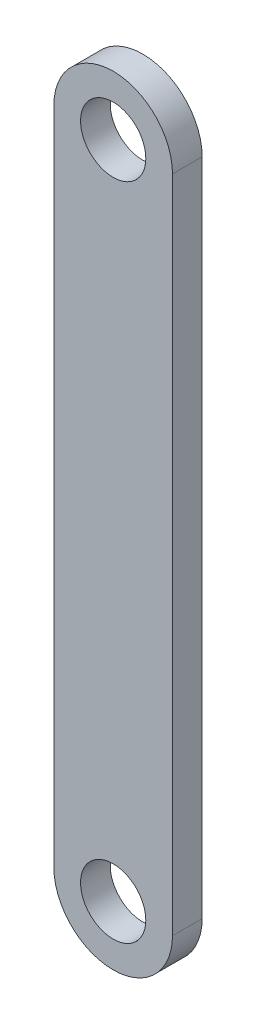
SolidWorks part; units mm, degrees
ref_plane "Спереди" through (0, 0, 0) normal (0, 0, 1) x (1, 0, 0)
ref_plane "Сверху" through (0, 0, 0) normal (0, 1, 0) x (1, 0, 0)
ref_plane "Справа" through (0, 0, 0) normal (1, 0, 0) x (0, 0, -1)
sketch "Model" plane through (0, 0, 0) normal (0, 0, 1) x (1, 0, 0)
  line L0 (0, 22.2444) -> (0, 0) construction
  line L1 (-2, 22.2444) -> (-2, 0)
  line L2 (2, 22.2444) -> (2, 0)
  circle A0 centre (0, 22.2444) radius 1.1
  arc A5 (2, 22.2444) -> (-2, 22.2444) centre (0, 22.2444) ccw
  arc A6 (-2, 0) -> (2, 0) centre (0, 0) ccw
  circle A8 centre (0, 0) radius 1.1
extrude "Extrude1" add sketch "Model" along normal blind 1 contours A0 A8 | L0 A5 L1 A6 | A5 L0 A6 L2 | A6 A8 region at (0, 11.1222, 0)
